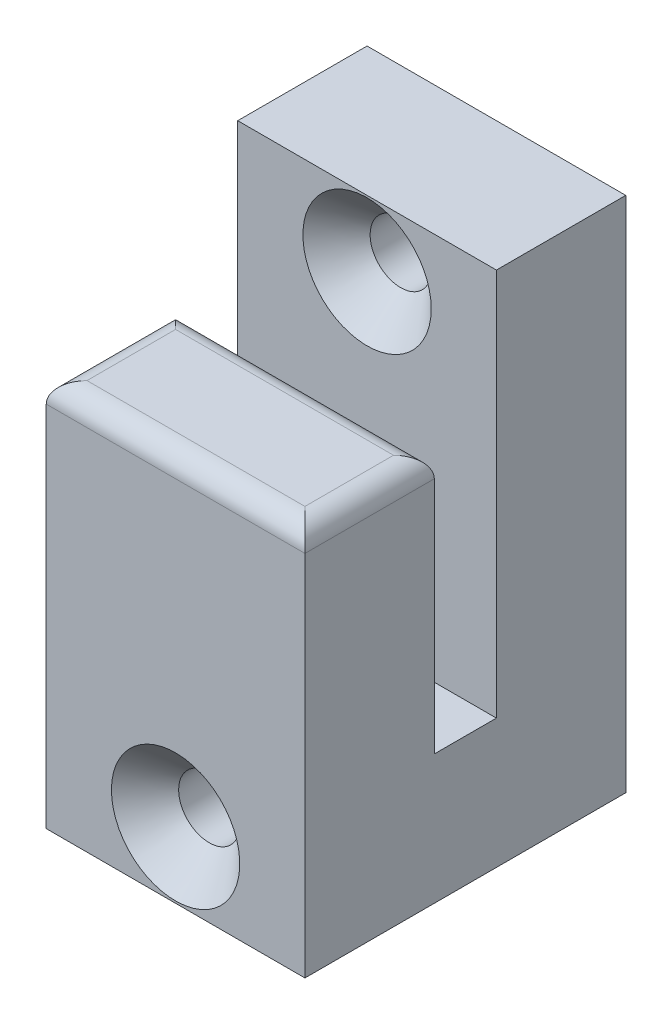
SolidWorks part; units mm, degrees
ref_plane "Front Plane" through (0, 0, 0) normal (0, 0, 1) x (1, 0, 0)
ref_plane "Top Plane" through (0, 0, 0) normal (0, 1, 0) x (1, 0, 0)
ref_plane "Right Plane" through (0, 0, 0) normal (1, 0, 0) x (0, 0, -1)
sketch "Sketch1" plane through (0, 0, 0) normal (1, 0, 0) x (0, 0, -1)
  line L0 (-0.8, 16.3286) -> (-13.5, 16.3286)
  line L1 (18, -21.7714) -> (-13.5, -21.7714)
  line L2 (18, -21.7714) -> (18, 29.0286)
  line L3 (18, 29.0286) -> (5.3, 29.0286)
  line L4 (-13.5, -21.7714) -> (-13.5, 16.3286)
  line L5 (18, -21.7714) -> (-13.5, 16.3286) construction
  line L6 (18, 29.0286) -> (-13.5, -21.7714) construction
  line L8 (5.3, 29.0286) -> (5.3, -9.0714)
  line L9 (5.3, -9.0714) -> (-0.8, -9.0714)
  line L10 (-0.8, 16.3286) -> (-0.8, -9.0714)
  line L11 (5.3, -9.0714) -> (5.3, -21.7714) construction
  point P0 (0, 0)
  dimension "D1" = 12.7
  dimension "D2" = 6.1
  dimension "D3" = 25.4
  dimension "D4" = 12.7
extrude "Boss-Extrude1" add sketch "Sketch1" along normal blind 25.4
sketch "Sketch2" plane through (0, 0, -18) normal (0, 0, -1) x (-1, 0, 0)
  line L0 (-12.7, 29.0286) -> (-12.7, -21.7714) construction
  line L1 (-25.4, 29.0286) -> (0, 29.0286) construction
  line L2 (-25.4, -21.7714) -> (0, -21.7714) construction
  line L3 (-12.7, 22.5286) -> (-12.7, 29.0286) construction
  line L4 (-12.7, -15.2714) -> (-12.7, -21.7714) construction
  circle A0 centre (-12.7, 22.5286) radius 3
  circle A1 centre (-12.7, -15.2714) radius 3
  dimension "D1" = 6
  dimension "D2" = 6.5
extrude "Cut-Extrude1" cut sketch "Sketch2" against normal through all
chamfer "Chamfer1" distance 3.3 angle 45 2 edges at (9.7, -15.2714, 13.5) (12.7, 25.5286, -5.3)
fillet "Fillet1" radius 2 4 edges at (12.7, 16.3286, 0.8) (25.4, 16.3286, 7.15) (12.7, 16.3286, 13.5) (0, 16.3286, 7.15)
